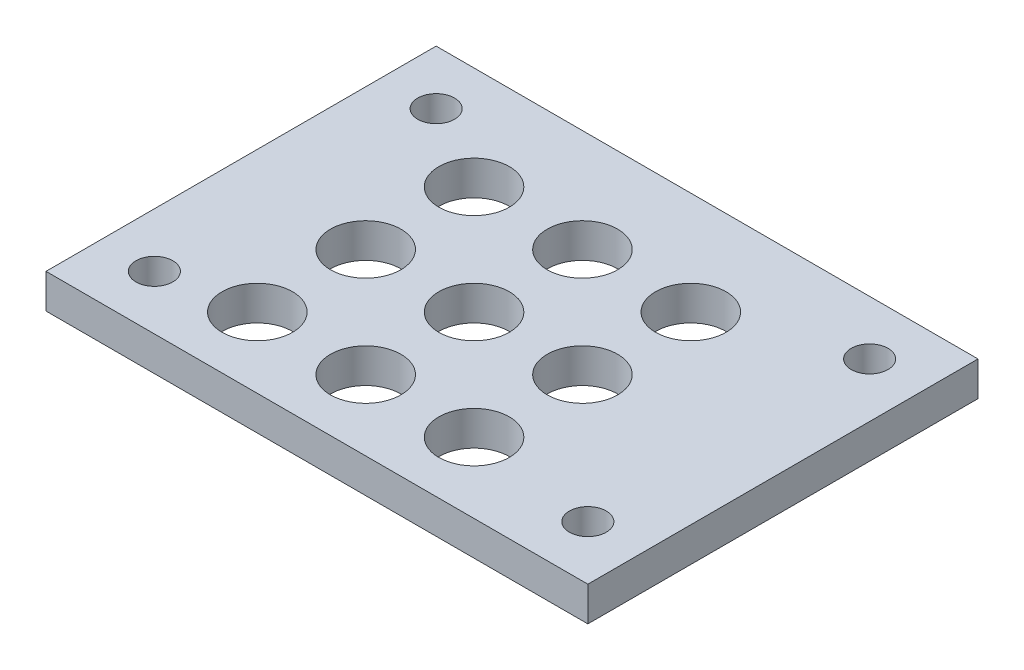
SolidWorks part; units mm, degrees
ref_plane "Front Plane" through (0, 0, 0) normal (0, 0, 1) x (1, 0, 0)
ref_plane "Top Plane" through (0, 0, 0) normal (0, 1, 0) x (1, 0, 0)
ref_plane "Right Plane" through (0, 0, 0) normal (1, 0, 0) x (0, 0, -1)
sketch "Sketch1" plane through (0, 0, 0) normal (0, 1, 0) x (1, 0, 0)
  line L0 (45, 31) -> (5, 31) construction
  line L1 (0, 0) -> (50, 0)
  line L2 (0, 0) -> (0, 36)
  line L3 (0, 36) -> (50, 36)
  line L4 (50, 0) -> (50, 36)
  line L6 (45, 31) -> (45, 5) construction
  circle A19 centre (13, 6.5) radius 3.25
  circle A28 centre (5, 5) radius 1.7
  circle A29 centre (5, 31) radius 1.7
  circle A30 centre (45, 31) radius 1.7
  circle A31 centre (45, 5) radius 1.7
  circle A32 centre (23, 6.5) radius 3.25
  circle A33 centre (33, 6.5) radius 3.25
  circle A34 centre (23, 16.5) radius 3.25
  circle A35 centre (33, 16.5) radius 3.25
  circle A36 centre (23, 26.5) radius 3.25
  circle A37 centre (33, 26.5) radius 3.25
  circle A38 centre (13, 16.5) radius 3.25
  circle A39 centre (13, 26.5) radius 3.25
  point P7 (45, 18)
  point P9 (25, 31)
  point P10 (25, 36)
  point P20 (50, 18)
  dimension "D5" = 40
  dimension "D6" = 26
  dimension "D3" = 6.5
  dimension "D8" = 3.4
  dimension "D1" = 50
  dimension "D2" = 36
  dimension "D4" = 8
  dimension "D7" = 1.5
  dimension "D9" = 3
extrude "Boss-Extrude1" add sketch "Sketch1" along normal blind 3.175 contours L1 L4 L3 L2 A39 A36 A34 region at (0.6161, 0, -18)
equation "\"o\"= 10mm"
equation "\"P\"= 10"
